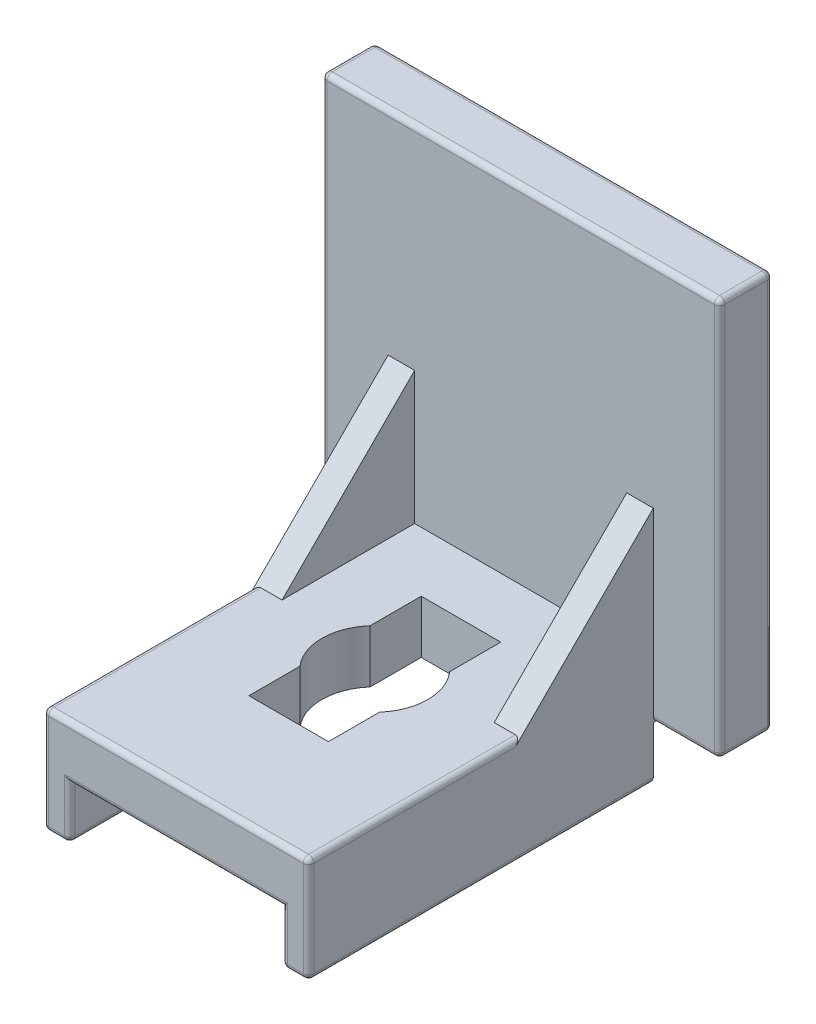
SolidWorks part; units mm, degrees
ref_plane "前视基准面" through (0, 0, 0) normal (0, 0, 1) x (1, 0, 0)
ref_plane "上视基准面" through (0, 0, 0) normal (0, 1, 0) x (1, 0, 0)
ref_plane "右视基准面" through (0, 0, 0) normal (1, 0, 0) x (0, 0, -1)
sketch "草图1" plane through (0, 0, 0) normal (0, 0, 1) x (1, 0, 0)
  line L1 (-7.5, 0) -> (7.5, 0)
  line L2 (-7.5, 0) -> (-7.5, 15)
  line L3 (-7.5, 15) -> (7.5, 15)
  line L4 (7.5, 0) -> (7.5, 15)
extrude "凸台-拉伸1" add sketch "草图1" along normal blind 2
sketch "草图2" plane through (0, 0, 0) normal (0, -1, 0) x (-1, 0, 0)
  line L0 (-4, -2) -> (-5, -2)
  line L1 (7.5, 0) -> (-4, 0)
  line L2 (7.5, 0) -> (7.5, -2)
  line L4 (-4, 0) -> (-4, -2)
  line L5 (5, -2) -> (7.5, -2)
  line L6 (5, -2) -> (5, -15)
  line L7 (5, -15) -> (-5, -15)
  line L8 (-5, -2) -> (-5, -15)
extrude "凸台-拉伸2" add sketch "草图2" against normal blind 2
sketch "草图4" plane through (0, 0, 0) normal (0, -1, 0) x (-1, 0, 0)
  line L0 (1.5, -8.8229) -> (1.5, -10.75)
  line L1 (1.5, -4.25) -> (-1.5, -4.25)
  line L2 (1.5, -4.25) -> (1.5, -6.1771)
  line L3 (1.5, -10.75) -> (-1.5, -10.75)
  line L4 (-1.5, -4.25) -> (-1.5, -6.1771)
  line L5 (-1.5, -8.8229) -> (-1.5, -10.75)
  arc A0 (1.5, -8.8229) -> (1.5, -6.1771) centre (0, -7.5) ccw
  arc A1 (-1.5, -6.1771) -> (-1.5, -8.8229) centre (0, -7.5) ccw
sketch "草图3" plane through (0, 0, 0) normal (0, -1, 0) x (-1, 0, 0)
  line L0 (-5, -15) -> (5, -15) construction
  line L1 (5, -2) -> (4, -2)
  line L2 (5, -2) -> (5, -15)
  line L3 (5, -15) -> (4, -15)
  line L4 (4, -2) -> (4, -15)
  line L6 (-5, -2) -> (-4, -2)
  line L7 (-5, -2) -> (-5, -15)
  line L8 (-5, -15) -> (-4, -15)
  line L9 (-4, -2) -> (-4, -15)
extrude "凸台-拉伸3" add sketch "草图3" along normal blind 2
extrude "切除-拉伸1" cut sketch "草图4" against normal up to next
sketch "草图5" plane through (0, 0, 0) normal (1, 0, 0) x (0, 0, -1)
  line L0 (-2, 2) -> (-7, 2)
  line L1 (-2, 2) -> (-15, 2) construction
  line L2 (-2, 2) -> (-2, 7)
  line L3 (-2, 0) -> (-2, 15) construction
  line L4 (-2, 7) -> (-7, 2)
extrude "凸台-拉伸4" add sketch "草图5" along normal blind 1 from offset 4
extrude "凸台-拉伸5" add sketch "草图5<2>" against normal blind 1 from offset 4 offset against normal yes
sketch "草图5<2>" plane through (0, 0, 0) normal (1, 0, 0) x (0, 0, -1) same geometry as "草图5"
sketch "草图6" plane through (0, 0, 0) normal (0, 0, -1) x (-1, 0, 0)
  line L1 (-1.5, 6) -> (1.5, 6)
  line L2 (-1.5, 6) -> (-1.5, 9)
  line L3 (-1.5, 9) -> (1.5, 9)
  line L4 (1.5, 6) -> (1.5, 9)
extrude "凸台-拉伸6" add sketch "草图6" along normal blind 1
sketch "草图7" plane through (0, 9, 0) normal (0, 1, 0) x (1, 0, 0)
  line L1 (-1.95, 2.5) -> (1.95, 2.5)
  line L2 (-1.95, 2.5) -> (-1.95, 1.5556)
  line L3 (-1.5, 1) -> (-1.5, 0) construction
  line L4 (1.95, 2.5) -> (1.95, 1.5556)
  line L5 (-1.5, 0.6771) -> (1.5, 0.6771)
  line L6 (1.5, 1) -> (1.5, 0) construction
  arc A0 (1.5, 0.6771) -> (1.95, 1.5556) centre (0, 2) ccw
  arc A1 (-1.95, 1.5556) -> (-1.5, 0.6771) centre (0, 2) ccw
extrude "凸台-拉伸7" add sketch "草图7" along normal blind 1 and the other way blind 4
sketch "草图8" plane through (-1.95, 0, 0) normal (-1, 0, 0) x (0, 0, 1)
  line L0 (-2.5, 5) -> (-2.5, 10) construction
  line L1 (-2.5, 9.45) -> (-1.5556, 9.45)
  line L2 (-2.5, 5.55) -> (-2.5, 5)
  line L3 (-2.5, 5.55) -> (-1.5556, 5.55)
  line L5 (-2.5, 5) -> (-0.6771, 5)
  line L6 (-0.6771, 5) -> (-0.6771, 6)
  line L7 (-2.5, 9.45) -> (-2.5, 10)
  line L8 (-2.5, 10) -> (-0.6771, 10)
  line L9 (-0.6771, 10) -> (-0.6771, 9)
  arc A0 (-0.6771, 9) -> (-1.5556, 9.45) centre (-2, 7.5) ccw
  arc A1 (-1.5556, 5.55) -> (-0.6771, 6) centre (-2, 7.5) ccw
extrude "切除-拉伸2" cut sketch "草图8" against normal up to next
fillet "圆角1" radius 0.1 4 edges at (1.95, 7.5, -2.5) (0, 9.45, -2.5) (-1.95, 7.5, -2.5) (0, 5.55, -2.5)
fillet "圆角4" radius 0.2 10 edges at (-7.5, 7.5, 0) (-7.5, 7.5, 2) (-7.5, 0, 1) (7.5, 0, 1) (7.5, 7.5, 2) (7.5, 7.5, 0) (7.5, 15, 1) (0, 15, 2) (-7.5, 15, 1) (0, 15, 0)
fillet "圆角5" radius 0.2 15 edges at (7.4414, 0.0586, 1.9414) (-7.4414, 0.0586, 1.9414) (-7.4414, 0.0586, 0.0586) (7.4414, 0.0586, 0.0586) (-4.5, -2, 15) (-5, 0, 15) (0, 2, 15) (5, 0, 15) (4.5, -2, 15) (4, -1, 15) (6.15, 0, 2) (-6.15, 0, 2) (0, 0, 0)
fillet "圆角6" radius 0.2 14 edges at (4.0586, -1.9414, 14.9414) (4.9414, -1.9414, 14.9414) (-4.9414, -1.9414, 14.9414) (-4.0586, -1.9414, 14.9414) (-4.9414, 1.9414, 14.9414) (4.9414, 1.9414, 14.9414) (4.5, -2, 2) (4, -2, 8.4) (5, -2, 8.4) (-4.5, -2, 2) (-5, -2, 8.4) (-4, -2, 8.4) (-5, 2, 10.9) (5, 2, 10.9)
